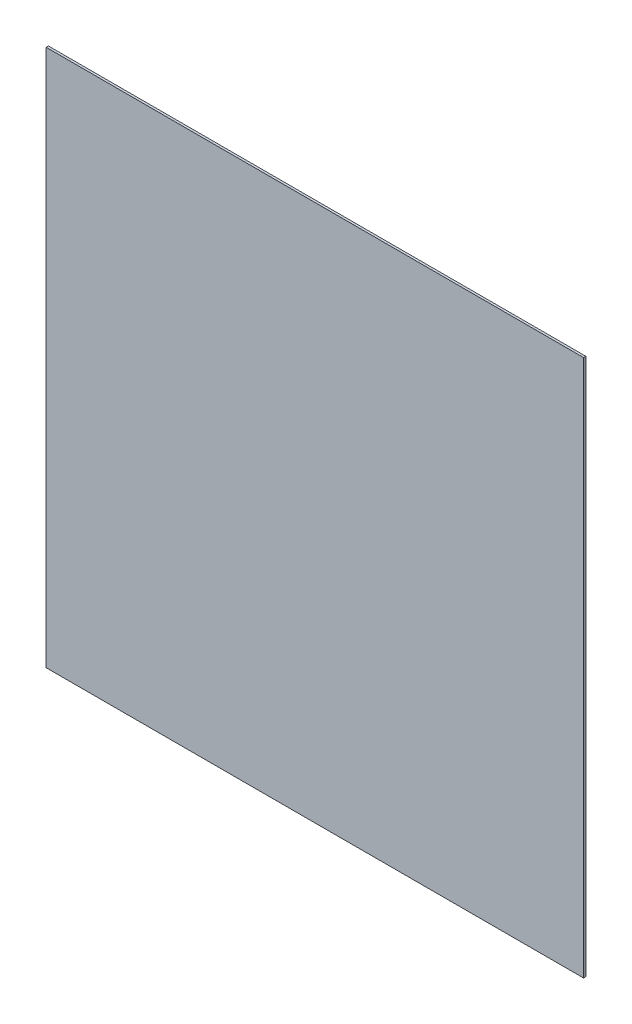
SolidWorks part; units mm, degrees
material "Mahogany"
ref_plane "Front Plane" through (0, 0, 0) normal (0, 0, 1) x (1, 0, 0)
ref_plane "Top Plane" through (0, 0, 0) normal (0, 1, 0) x (1, 0, 0)
ref_plane "Right Plane" through (0, 0, 0) normal (1, 0, 0) x (0, 0, -1)
sketch "Sketch1" plane through (0, 0, 0) normal (0, 0, 1) x (1, 0, 0)
  line L1 (-375, 375) -> (375, 375)
  line L2 (-375, 375) -> (-375, -375)
  line L3 (-375, -375) -> (375, -375)
  line L4 (375, 375) -> (375, -375)
  line L5 (-375, 375) -> (375, -375) construction
  line L6 (-375, -375) -> (375, 375) construction
  point P0 (0, 0)
  dimension "D1" = 750
  dimension "D2" = 750
extrude "Boss-Extrude1" add sketch "Sketch1" along normal blind 3.175
equation "\"W\"= 1500"
equation "\"L\"= 780"
equation "\"H\"= 780"
equation "\"ARM_BOLT_SPACING\"= 166"
equation "\"ARM_TO_WALL\"= 200"
equation "\"D1@Sketch1\"=\"L\"-30"
equation "\"D2@Sketch1\"=\"H\"-30"
